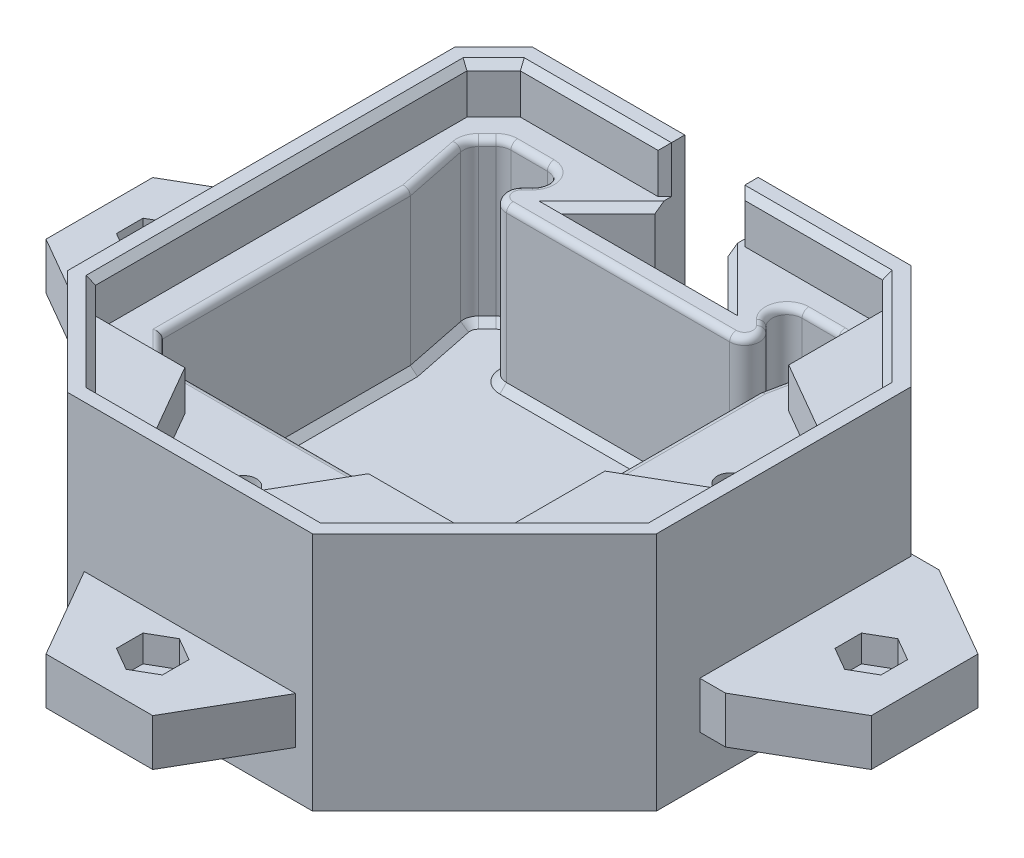
SolidWorks part; units mm, degrees
ref_plane "Front Plane" through (0, 0, 0) normal (0, 0, 1) x (1, 0, 0)
ref_plane "Top Plane" through (0, 0, 0) normal (0, 1, 0) x (1, 0, 0)
ref_plane "Right Plane" through (0, 0, 0) normal (1, 0, 0) x (0, 0, -1)
sketch "Sketch2" plane through (0, 0, 0) normal (0, 1, 0) x (1, 0, 0)
  line L0 (17.15, -41.8374) -> (-17.15, -41.8374)
  line L1 (41.15, -17.8374) -> (41.15, 17.8374)
  line L2 (27.15, 31.8374) -> (-27.15, 31.8374)
  line L3 (-31.15, -27.8374) -> (-31.15, 27.8374)
  line L4 (-17.15, -41.8374) -> (-31.15, -27.8374)
  line L5 (41.15, -17.8374) -> (17.15, -41.8374)
  line L6 (-27.15, 31.8374) -> (-31.15, 27.8374)
  line L7 (41.15, 17.8374) -> (27.15, 31.8374)
  point P0 (41.15, -41.8374)
  point P1 (-31.15, 31.8374)
  point P2 (41.15, 31.8374)
  point P3 (-31.15, -41.8374)
  point P15 (0, 31.8374)
  point P17 (41.15, 0)
  dimension "D1" = 73.6748
  dimension "D2" = 72.3
  dimension "D3" = 14
  dimension "D4" = 14
  dimension "D5" = 24
  dimension "D6" = 24
  dimension "D7" = 4
  dimension "D8" = 4
  dimension "D9" = 14
  dimension "D10" = 14
extrude "Boss-Extrude1" add sketch "Sketch2" along normal blind 6 and the other way blind 29
sketch "Sketch3" plane through (0, 6, 0) normal (0, 1, 0) x (1, 0, 0)
  line L5 (-8, -41.8374) -> (-13.7735, -31.8374)
  line L6 (-17.15, -41.8374) -> (17.15, -41.8374) construction
  line L7 (-13.7735, -31.8374) -> (13.7735, -31.8374)
  line L8 (13.7735, -31.8374) -> (8, -41.8374)
  line L9 (8, -41.8374) -> (-8, -41.8374)
  line L10 (41.15, -8) -> (41.15, 8)
  line L11 (41.15, -17.8374) -> (41.15, 17.8374) construction
  line L12 (41.15, 8) -> (31.15, 13.7735)
  line L13 (31.15, 13.7735) -> (31.15, -13.7735)
  line L14 (31.15, -13.7735) -> (41.15, -8)
  point P14 (0, -31.8374)
  point P21 (31.15, 0)
  dimension "D4" = 60
  dimension "D5" = 60
  dimension "D6" = 10
  dimension "D7" = 16
  dimension "D9" = 60
  dimension "D10" = 60
  dimension "D11" = 16
  dimension "D12" = 10
extrude "Cut-Extrude1" cut sketch "Sketch3" against normal blind 6
sketch "Sketch4" plane through (0, 6, 0) normal (0, 1, 0) x (1, 0, 0)
  line L0 (27.15, 31.8374) -> (-27.15, 31.8374) construction
  line L1 (-5.5, 31.8374) -> (5.5, 31.8374)
  line L2 (-5.5, 31.8374) -> (-5.5, 30.3374)
  line L3 (-5.5, 30.3374) -> (5.5, 30.3374) construction
  line L4 (5.5, 31.8374) -> (5.5, 30.3374)
  line L5 (-5.5, 30.3374) -> (-12.5, 23.3374)
  line L6 (-11.5, 24.3374) -> (11.5, 24.3374) construction
  line L7 (-12.5, 23.3374) -> (12.5, 23.3374)
  line L8 (12.5, 23.3374) -> (5.5, 30.3374)
  point P6 (0, 30.3374)
  dimension "D1" = 45
  dimension "D2" = 11
  dimension "D3" = 1.5
  dimension "D4" = 45
  dimension "D5" = 23
  dimension "D6" = 1
extrude "Cut-Extrude2" cut sketch "Sketch4" against normal through all both and the other way through all
sketch "Sketch5" plane through (0, 0, 0) normal (0, 1, 0) x (1, 0, 0)
  line L1 (-8, -41.8374) -> (8, -41.8374) construction
  line L2 (41.15, -8) -> (41.15, 8) construction
  circle A0 centre (36.15, 0) radius 1.95
  circle A1 centre (0, -36.8374) radius 1.95
  dimension "D1" = 3.9
  dimension "D2" = 3.9
  dimension "D3" = 5
  dimension "D4" = 5
extrude "Cut-Extrude3" cut sketch "Sketch5" against normal blind 12
sketch "Sketch6" plane through (0, 6, 0) normal (0, 1, 0) x (1, 0, 0)
  line L1 (31.15, 31.8374) -> (-31.15, 31.8374)
  line L2 (31.15, 31.8374) -> (31.15, -31.8374)
  line L3 (31.15, -31.8374) -> (-31.15, -31.8374)
  line L4 (-31.15, 31.8374) -> (-31.15, -31.8374)
  line L5 (13.7735, -31.8374) -> (-13.7735, -31.8374) construction
  line L7 (-5.5, 31.8374) -> (-27.15, 31.8374) construction
  line L8 (31.15, 13.7735) -> (31.15, -13.7735) construction
  line L9 (-31.15, 27.8374) -> (-31.15, -27.8374) construction
extrude "Cut-Extrude4" cut sketch "Sketch6" against normal blind 6
sketch "Sketch7" plane through (0, 0, 0) normal (0, 1, 0) x (1, 0, 0)
  line L5 (-22.15, 18.3374) -> (22.15, 18.3374) construction
  line L6 (-26.15, 14.3374) -> (-26.15, -22.8374)
  line L7 (-22.15, -26.8374) -> (22.15, -26.8374)
  line L8 (26.15, 14.3374) -> (26.15, -22.8374)
  line L9 (-27.15, -31.8374) -> (-13.7735, -31.8374) construction
  line L12 (-26.15, 14.3374) -> (-22.15, 18.3374) construction
  line L13 (-26.15, -22.8374) -> (-22.15, -26.8374)
  line L14 (22.15, -26.8374) -> (26.15, -22.8374)
  line L15 (22.15, 18.3374) -> (26.15, 14.3374) construction
  line L16 (31.15, -27.8374) -> (31.15, -13.7735) construction
  line L17 (-31.15, 27.8374) -> (-31.15, -27.8374) construction
  line L19 (-12.5, 23.3374) -> (12.5, 23.3374) construction
  line L80 (-26.15, 14.3374) -> (-28.3216, 25.009)
  line L81 (26.15, 14.3374) -> (28.3216, 25.009)
  line L89 (28.3216, 25.009) -> (25.4931, 27.8374)
  line L90 (25.4931, 27.8374) -> (13.6569, 27.8374)
  line L91 (-25.4931, 27.8374) -> (-28.3216, 25.009)
  line L92 (-13.6569, 27.8374) -> (-25.4931, 27.8374)
  line L93 (13.6569, 27.8374) -> (22.1569, 19.3374)
  line L94 (22.1569, 19.3374) -> (-22.1569, 19.3374)
  line L95 (-22.1569, 19.3374) -> (-13.6569, 27.8374)
  line L96 (28.3216, 25.009) -> (25.4931, 27.8374)
  line L97 (25.4931, 27.8374) -> (13.6569, 27.8374)
  line L98 (-25.4931, 27.8374) -> (-28.3216, 25.009)
  line L99 (-13.6569, 27.8374) -> (-25.4931, 27.8374)
  line L100 (13.6569, 27.8374) -> (22.1569, 19.3374)
  line L101 (22.1569, 19.3374) -> (-22.1569, 19.3374)
  line L102 (-22.1569, 19.3374) -> (-13.6569, 27.8374)
  point P0 (-26.15, 18.3374)
  point P1 (26.15, -26.8374)
  point P2 (-26.15, -26.8374)
  point P3 (26.15, 18.3374)
  dimension "D2" = 5
  dimension "D3" = 5
  dimension "D4" = 5
  dimension "D5" = 5
  dimension "D6" = 4
extrude "Cut-Extrude5" cut sketch "Sketch7" against normal offset from surface (24 mm away) 5 up to face at (1.4286, -29, -10.7875)
sketch "Sketch8" plane through (0, -29, 0) normal (0, -1, 0) x (1, 0, 0)
  line L5 (28.3926, -34.8374) -> (44.15, -19.08)
  line L6 (44.15, -19.08) -> (44.15, 19.08)
  line L7 (44.15, 19.08) -> (18.3926, 44.8374)
  line L8 (18.3926, 44.8374) -> (-18.3926, 44.8374)
  line L9 (-18.3926, 44.8374) -> (-34.15, 29.08)
  line L10 (-34.15, 29.08) -> (-34.15, -29.08)
  line L11 (-34.15, -29.08) -> (-28.3926, -34.8374)
  line L12 (-27.15, -31.8374) -> (-5.5, -31.8374)
  line L13 (-5.5, -31.8374) -> (-5.5, -30.3374)
  line L15 (5.5, -30.3374) -> (5.5, -31.8374)
  line L16 (5.5, -31.8374) -> (27.15, -31.8374)
  line L17 (27.15, -31.8374) -> (41.15, -17.8374)
  line L18 (41.15, -17.8374) -> (41.15, 17.8374)
  line L19 (41.15, 17.8374) -> (17.15, 41.8374)
  line L20 (17.15, 41.8374) -> (-17.15, 41.8374)
  line L21 (-17.15, 41.8374) -> (-31.15, 27.8374)
  line L22 (-31.15, 27.8374) -> (-31.15, -27.8374)
  line L23 (-31.15, -27.8374) -> (-27.15, -31.8374)
  line L24 (-27.15, -31.8374) -> (-5.5, -31.8374)
  line L28 (5.5, -31.8374) -> (27.15, -31.8374)
  line L29 (27.15, -31.8374) -> (41.15, -17.8374)
  line L30 (41.15, -17.8374) -> (41.15, 17.8374)
  line L31 (41.15, 17.8374) -> (17.15, 41.8374)
  line L32 (17.15, 41.8374) -> (-17.15, 41.8374)
  line L33 (-17.15, 41.8374) -> (-31.15, 27.8374)
  line L34 (-31.15, 27.8374) -> (-31.15, -27.8374)
  line L35 (-31.15, -27.8374) -> (-27.15, -31.8374)
  line L36 (-28.3926, -34.8374) -> (-5.5, -34.8374)
  line L37 (-5.5, -34.8374) -> (-5.5, -31.8374)
  line L38 (28.3926, -34.8374) -> (5.5, -34.8374)
  line L39 (5.5, -34.8374) -> (5.5, -31.8374)
  line L50 (-5.5, -30.3374) -> (5.5, -30.3374) construction
  line L56 (-2.5, -34.8374) -> (-2.5, -33.3374) construction
  line L57 (-5.5, -31.8374) -> (-5.5, -30.3374) construction
  line L58 (-2.5, -33.3374) -> (2.5, -33.3374) construction
  line L59 (5.5, -30.3374) -> (5.5, -31.8374) construction
  line L60 (2.5, -33.3374) -> (2.5, -34.8374) construction
  line L61 (2.5, -34.8374) -> (28.3926, -34.8374) construction
  line L62 (-28.3926, -34.8374) -> (-2.5, -34.8374) construction
  line L65 (-12.5, -23.3374) -> (12.5, -23.3374)
  line L66 (-5.5, -30.3374) -> (-12.5, -23.3374)
  line L69 (12.5, -23.3374) -> (5.5, -30.3374)
  dimension "D1" = 0
  dimension "D2" = 3
extrude "Boss-Extrude2" add sketch "Sketch8" against normal blind 36
chamfer "Chamfer1" distance 1 angle 45 9 edges at (-16.325, 7, -31.8374) (16.325, 7, -31.8374) (34.15, 7, -24.8374) (41.15, 7, 0) (29.15, 7, 29.8374) (0, 7, 41.8374) (-24.15, 7, 34.8374) (-31.15, 7, 0) (-29.15, 7, -29.8374)
fillet "Fillet2" radius 2.25 8 edges at (13.6569, -12, -27.8374) (-13.6569, -12, -27.8374) (22.1569, -12, -19.3374) (-22.1569, -12, -19.3374) (28.3216, -12, -25.009) (25.4931, -12, -27.8374) (-28.3216, -12, -25.009) (-25.4931, -12, -27.8374)
fillet "Fillet1" radius 1 22 edges at (-24.15, 0, 24.8374) (0, 0, 26.8374) (24.15, 0, 24.8374) (26.15, 0, 4.25) (-26.15, 0, 4.25) (-21.825, 0, -27.8374) (-26.8094, 0, -26.5211) (-27.1152, 0, -19.0808) (-17.9069, 0, -23.5874) (0, 0, -19.3374) (17.9069, 0, -23.5874) (21.825, 0, -27.8374) (26.8094, 0, -26.5211) (27.1152, 0, -19.0808) (-28.0302, 0, -24.9213) (-25.4222, 0, -27.6661) (-17.0101, 0, -26.4484) (-18.8036, 0, -20.7264) (18.8036, 0, -20.7264) (17.0101, 0, -26.4484) (25.4222, 0, -27.6661) (28.0302, 0, -24.9213)
chamfer "Chamfer3" distance 1 angle 45 22 edges at (26.15, -24, 4.25) (24.15, -24, 24.8374) (0, -24, 26.8374) (-24.15, -24, 24.8374) (-26.15, -24, 4.25) (-26.8094, -24, -26.5211) (-21.825, -24, -27.8374) (-17.9069, -24, -23.5874) (0, -24, -19.3374) (17.9069, -24, -23.5874) (21.825, -24, -27.8374) (26.8094, -24, -26.5211) (27.1152, -24, -19.0808) (-27.1152, -24, -19.0808) (-28.0302, -24, -24.9213) (-25.4222, -24, -27.6661) (-17.0101, -24, -26.4484) (-18.8036, -24, -20.7264) (18.8036, -24, -20.7264) (17.0101, -24, -26.4484) (25.4222, -24, -27.6661) (28.0302, -24, -24.9213)
chamfer "Chamfer5" distance 1 angle 45 5 edges at (5.5, 3, -31.8374) (-5.5, 3, -31.8374) (9, 0, -26.8374) (0, 0, -23.3374) (-9, 0, -26.8374)
sketch "Sketch10" plane through (0, -24, 0) normal (0, 1, 0) x (1, 0, 0)
  line L0 (-32.15, -28.2516) -> (-32.15, 28.2516) construction
  line L1 (-9.8995, -6.4621) -> (9.8995, -6.4621) construction
  line L2 (-9.8995, -6.4621) -> (-9.8995, 13.3369) construction
  line L3 (-9.8995, 13.3369) -> (9.8995, 13.3369) construction
  line L4 (9.8995, -6.4621) -> (9.8995, 13.3369) construction
  line L5 (-9.8995, -6.4621) -> (9.8995, 13.3369) construction
  line L6 (-9.8995, 13.3369) -> (9.8995, -6.4621) construction
  circle A0 centre (0, 3.4374) radius 14 construction
  circle A1 centre (-9.8995, 13.3369) radius 2
  circle A2 centre (9.8995, 13.3369) radius 2
  circle A3 centre (-9.8995, -6.4621) radius 2
  circle A4 centre (9.8995, -6.4621) radius 2
  dimension "D1" = 28
  dimension "D2" = 4
  dimension "D3" = 4
  dimension "D4" = 4
  dimension "D5" = 4
  dimension "D6" = 3.4374
  dimension "D7" = 22.2505
sketch "Sketch12" plane through (0, -29, 0) normal (0, -1, 0) x (1, 0, 0)
  line L0 (-999.7733, -3.4374) -> (49000.2267, -3.4374) construction
  line L1 (-48, 12.5626) -> (-34.1436, 12.5626)
  line L2 (0, -1002.6874) -> (0, 48997.3126) construction
  line L15 (-48, 12.5626) -> (-61.8564, 4.5626)
  line L16 (-61.8564, 4.5626) -> (-61.8564, -11.4374)
  line L17 (-61.8564, -11.4374) -> (-48, -19.4374)
  line L18 (-48, -19.4374) -> (-34.1436, -11.4374) construction
  line L19 (-34.1436, -11.4374) -> (-34.1436, 4.5626)
  line L20 (-34.1436, 4.5626) -> (-48, 12.5626) construction
  line L21 (-34.1436, 12.5626) -> (-34.1436, 4.5626)
  line L22 (-34.1436, -11.4374) -> (-34.1436, -19.4374)
  line L23 (-34.1436, -19.4374) -> (-48, -19.4374)
  line L24 (16, 44.5626) -> (16, 30.7062)
  line L25 (16, 44.5626) -> (8, 58.419)
  line L26 (8, 58.419) -> (-8, 58.419)
  line L27 (-8, 58.419) -> (-16, 44.5626)
  line L28 (-8, 30.7062) -> (8, 30.7062)
  line L29 (16, 30.7062) -> (8, 30.7062)
  line L30 (-8, 30.7062) -> (-16, 30.7062)
  line L31 (-16, 30.7062) -> (-16, 44.5626)
  line L32 (-16, 44.5626) -> (-8, 30.7062) construction
  line L33 (8, 30.7062) -> (16, 44.5626) construction
  line L34 (48, -19.4374) -> (34.1436, -19.4374)
  line L35 (48, -19.4374) -> (61.8564, -11.4374)
  line L36 (61.8564, -11.4374) -> (61.8564, 4.5626)
  line L37 (61.8564, 4.5626) -> (48, 12.5626)
  line L38 (34.1436, 4.5626) -> (34.1436, -11.4374)
  line L39 (34.1436, -19.4374) -> (34.1436, -11.4374)
  line L40 (34.1436, 4.5626) -> (34.1436, 12.5626)
  line L41 (34.1436, 12.5626) -> (48, 12.5626)
  line L42 (48, 12.5626) -> (34.1436, 4.5626) construction
  line L43 (34.1436, -11.4374) -> (48, -19.4374) construction
  line L44 (-16, -51.4374) -> (-16, -37.581) [skipped]
  line L45 (-16, -51.4374) -> (-8, -65.2938) [skipped]
  line L46 (-8, -65.2938) -> (8, -65.2938) [skipped]
  line L47 (8, -65.2938) -> (16, -51.4374) [skipped]
  line L48 (8, -37.581) -> (-8, -37.581) [skipped]
  line L49 (-16, -37.581) -> (-8, -37.581) [skipped]
  line L50 (8, -37.581) -> (16, -37.581) [skipped]
  line L51 (16, -37.581) -> (16, -51.4374) [skipped]
  line L52 (16, -51.4374) -> (8, -37.581) construction
  line L53 (-8, -37.581) -> (-16, -51.4374) construction
  circle A2 centre (-48, -3.4374) radius 13.8564 construction
  circle A3 centre (0, 44.5626) radius 13.8564 construction
  circle A4 centre (48, -3.4374) radius 13.8564 construction
  circle A5 centre (0, -51.4374) radius 13.8564 construction
  circle A6 centre (-53.8564, -3.4374) radius 2
  circle A7 centre (0, 50.419) radius 2
  circle A8 centre (53.8564, -3.4374) radius 2
  circle A9 centre (0, -57.2938) radius 2 [skipped]
  point P14 (0, -3.4374)
  point P49 (0, -3.4374)
  point P58 (0, -3.4374)
  dimension "D4" = 4
  dimension "D1" = 16
  dimension "D2" = 48
  dimension "D3" = 8
extrude "Boss-Extrude3" add sketch "Sketch12" against normal blind 7 from offset 7 offset against normal yes
sketch "Sketch15" plane through (0, -29, 0) normal (0, -1, 0) x (1, 0, 0)
  line L1 (-50.4064, -1.4455) -> (-53.8564, 0.5463)
  line L2 (-53.8564, 0.5463) -> (-57.3064, -1.4455)
  line L3 (-57.3064, -1.4455) -> (-57.3064, -5.4293)
  line L4 (-57.3064, -5.4293) -> (-53.8564, -7.4211)
  line L5 (-53.8564, -7.4211) -> (-50.4064, -5.4293)
  line L6 (-50.4064, -5.4293) -> (-50.4064, -1.4455)
  line L7 (0, 54.4027) -> (-3.45, 52.4109)
  line L8 (-3.45, 52.4109) -> (-3.45, 48.4271)
  line L9 (-3.45, 48.4271) -> (0, 46.4353)
  line L10 (0, 46.4353) -> (3.45, 48.4271)
  line L11 (3.45, 48.4271) -> (3.45, 52.4109)
  line L12 (3.45, 52.4109) -> (0, 54.4027)
  line L13 (53.8564, 0.5463) -> (50.4064, -1.4455)
  line L14 (50.4064, -1.4455) -> (50.4064, -5.4293)
  line L15 (50.4064, -5.4293) -> (53.8564, -7.4211)
  line L16 (53.8564, -7.4211) -> (57.3064, -5.4293)
  line L17 (57.3064, -5.4293) -> (57.3064, -1.4455)
  line L18 (57.3064, -1.4455) -> (53.8564, 0.5463)
  circle A0 centre (-53.8564, -3.4374) radius 3.45 construction
  circle A1 centre (0, 50.419) radius 3.45 construction
  circle A2 centre (53.8564, -3.4374) radius 3.45 construction
  dimension "D1" = 6.9
  dimension "D2" = 6.9
  dimension "D3" = 6.9
extrude "Cut-Extrude8" cut sketch "Sketch15" along normal blind 4 from surface starting at face at (-53.8564, -15, -5.4374)
